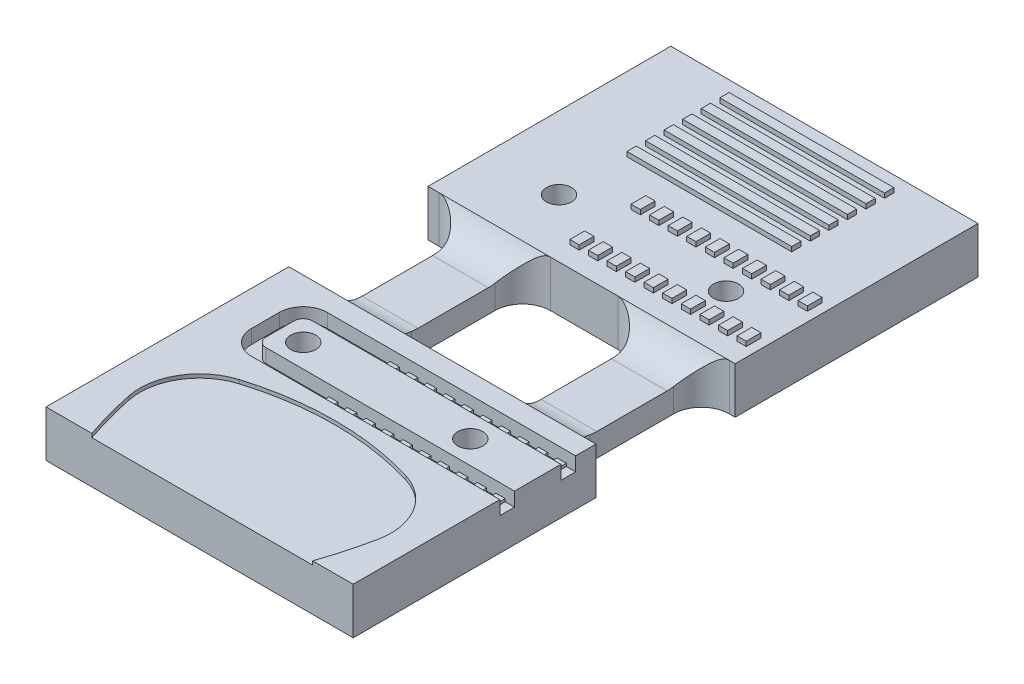
SolidWorks part; units mm, degrees
ref_plane "Front Plane" through (0, 0, 0) normal (0, 0, 1) x (1, 0, 0)
ref_plane "Top Plane" through (0, 0, 0) normal (0, 1, 0) x (1, 0, 0)
ref_plane "Right Plane" through (0, 0, 0) normal (1, 0, 0) x (0, 0, -1)
sketch "Pick" plane through (0, 0, 0) normal (0, 1, 0) x (1, 0, 0)
  line L0 (0, 0) -> (0, 30.62) construction
  line L1 (-13.11, 22.1848) -> (0, 22.1848) construction
  line L2 (0, 22.1848) -> (13.11, 22.1848) construction
  line L3 (0, 2.9) -> (-2.9, 2.9) construction
  line L6 (9.0762, 10.7993) -> (9.4821, 11.5846) construction
  line L7 (-7.0973, 23.4286) -> (-12.0562, 27.0493) construction
  arc A0 (-8.8774, 29.3049) -> (8.8774, 29.3049) centre (0, 0) cw
  arc A1 (-2.1219, 0.9232) -> (-13.11, 22.1848) centre (30.3499, 31.175) cw
  arc A2 (-13.11, 22.1848) -> (-8.8774, 29.3049) centre (-7.0973, 23.4286) cw
  arc A3 (2.1219, 0.9232) -> (13.11, 22.1848) centre (-30.3499, 31.175) ccw
  arc A4 (13.11, 22.1848) -> (8.8774, 29.3049) centre (7.0973, 23.4286) ccw
  arc A5 (-2.1219, 0.9232) -> (2.1219, 0.9232) centre (0, 2.9) ccw
  circle A6 centre (-7.0973, 23.4286) radius 6.14 construction
  circle A7 centre (-30.3499, 31.175) radius 44.38 construction
  circle A8 centre (0, 2.9) radius 2.9 construction
  point P8 (0, 30.62)
  dimension "D1" = 30.62
  dimension "D2" = 26.22
  dimension "D3" = 44.38
  dimension "D4" = 6.14
  dimension "D5" = 2.9
sketch "Sketch3" plane through (0, 0, 0) normal (0, 1, 0) x (1, 0, 0)
  line L0 (-11.8929, 16.62) -> (11.8929, 16.62)
  line L1 (-13.11, 22.1848) -> (-14, 26.4873) construction
  line L2 (0, 16.62) -> (0, 22.1848) construction
  line L3 (0, 22.1848) -> (13.11, 22.1848) construction
  line L4 (0, 0) -> (0, 30.62) construction
  line L5 (0, 30.92) -> (0, 30.62) construction
  line L6 (-11.8929, 16.62) -> (-10.1999, 11.7063) construction
  line L7 (-13.11, 22.1848) -> (-13.4038, 22.124) construction
  line L8 (-11.8929, 16.62) -> (-11.6093, 16.7177) construction
  line L9 (-8.8774, 29.3049) -> (-11.642, 28.4674) construction
  line L10 (-8.8774, 29.3049) -> (-8.9644, 29.592) construction
  line L11 (-11.8929, 16.62) -> (-16.8356, 16.62)
  line L12 (-16.8356, 16.62) -> (-16.8356, 42.7863)
  line L13 (-16.8356, 42.7863) -> (16.2633, 42.7863)
  line L14 (16.2633, 42.7863) -> (16.2633, 16.62)
  line L15 (16.2633, 16.62) -> (11.8929, 16.62)
  line L16 (0, 40.595) -> (0, 42.7863) construction
  line L17 (0, 30.62) -> (0, 22.1848) construction
  line L33 (16.2633, 32.42) -> (-10.5, 32.42)
  line L34 (-13.0875, 35.0075) -> (-13.0875, 38.0075)
  line L35 (-11.5, 35.0075) -> (-11.5, 38.0075)
  line L36 (-10.5, 34.0075) -> (16.2633, 34.0075)
  line L37 (16.2633, 34.0075) -> (16.2633, 32.42)
  line L38 (-10.5, 39.0075) -> (16.2633, 39.0075)
  line L39 (16.2633, 39.0075) -> (16.2633, 40.595)
  line L40 (16.2633, 40.595) -> (-10.5, 40.595)
  line L41 (-13.0875, 35.0075) -> (-11.5, 35.0075) construction
  line L42 (-11.5, 38.0075) -> (-13.0875, 38.0075) construction
  line L43 (0, 30.92) -> (0, 32.42) construction
  line L44 (0, 34.0075) -> (0, 36.5075) construction
  line L45 (-9, 36.5075) -> (9, 36.5075) construction
  line L46 (-9, 36.5075) -> (-11.5, 36.5075) construction
  line L47 (0, 36.5075) -> (0, 39.0075) construction
  arc A0 (-11.8929, 16.62) -> (-13.4038, 22.124) centre (30.3499, 31.175) cw
  arc A1 (2.1219, 0.9232) -> (13.11, 22.1848) centre (-30.3499, 31.175) ccw construction
  arc A2 (11.8929, 16.62) -> (13.4038, 22.124) centre (-30.3499, 31.175) ccw
  arc A3 (-8.9644, 29.592) -> (8.9644, 29.592) centre (0, 0) cw
  arc A4 (-13.11, 22.1848) -> (-2.1219, 0.9232) centre (30.3499, 31.175) ccw construction
  arc A5 (8.8774, 29.3049) -> (-8.8774, 29.3049) centre (0, 0) ccw construction
  arc A7 (-13.4038, 22.124) -> (-8.9644, 29.592) centre (-7.0973, 23.4286) cw
  arc A8 (8.9644, 29.592) -> (13.4038, 22.124) centre (7.0973, 23.4286) cw
  arc A12 (-10.5, 34.0075) -> (-11.5, 35.0075) centre (-10.5, 35.0075) cw
  arc A13 (-10.5, 32.42) -> (-13.0875, 35.0075) centre (-10.5, 35.0075) cw
  arc A14 (-11.5, 38.0075) -> (-10.5, 39.0075) centre (-10.5, 38.0075) cw
  arc A15 (-10.5, 40.595) -> (-13.0875, 38.0075) centre (-10.5, 38.0075) ccw
  point P26 (-9, 36.5075)
  point P38 (0, 42.7863)
  point P42 (9, 36.5075)
  point P95 (0, 36.5075)
  dimension "D2" = 0.3
  dimension "D3" = 18
  dimension "D7" = 1
  dimension "D1" = 14
  dimension "D8" = 1.5875
  dimension "D9" = 1.5
  dimension "D10" = 2.5
extrude "Boss-Extrude1" add sketch "Sketch3" against normal blind 0.4 contours A3 A8 A2 L15 L14 L13 L12 L11 A0 A7 | L40 A15 L34 A13 L33 L14 L36 A12 L35 A14 L38 | A14 L35 A12 L36 L14 L38 region at (-2.3245, 0, -31.7034) region at (2.8816, 0, -32.7247) region at (2.424, 0, -36.5075)
extrude "Boss-Extrude4" add sketch "Sketch3<5>" against normal blind 4.6 from surface contours A3 A8 A2 L15 L14 L13 L12 L11 A0 A7 | A8 A3 A7 A0 L0 A2 | L40 A15 L34 A13 L33 L14 L36 A12 L35 A14 L38 | A14 L35 A12 L36 L14 L38 region at (0, 0, -23.3328) region at (-2.3245, 0, -31.7034) region at (2.8816, 0, -32.7247) region at (2.424, 0, -36.5075) starting at face at (-0.1145, -0.4, -25.8487)
sketch "Sketch3<5>" plane through (0, 0, 0) normal (0, 1, 0) x (1, 0, 0) same geometry as "Sketch3"
extrude "Cut-Extrude2" cut sketch "Sketch3<7>" against normal blind 1.5 contours L40 A15 L34 A13 L33 L14 L36 A12 L35 A14 L38 region at (2.8816, 0, -32.7247)
sketch "Sketch3<7>" plane through (0, 0, 0) normal (0, 1, 0) x (1, 0, 0) same geometry as "Sketch3"
hole_wizard "M2.5 Clearance Hole1" positions "Sketch6" profile "Sketch7" hole size "M2.5" standard "ANSI Metric"
sketch "Sketch6" plane through (0, 0, 0) normal (0, 1, 0) x (1, 0, 0)
  point P0 (-9, 36.5075)
  point P3 (9, 36.5075)
sketch "Sketch7" plane through (-9, 0, -36.5075) normal (1, 0, 0) x (0, 0, 1)
  line L0 (0, 0) -> (0, 12)
  line L1 (0, 12) -> (1.35, 11.1888)
  line L2 (1.35, 11.1888) -> (1.35, 0)
  line L5 (1.35, 0) -> (0, 0)
  line L10 (0, 12) -> (-1.35, 11.1888) construction
  line L11 (0, -6.35) -> (0, 107.95) construction
  dimension "Hole Dia." = 2.7
  dimension "Hole Depth" = 12
  dimension "Drill Angle" = 118
sketch "Sketch8" plane through (0, 0, 0) normal (0, 1, 0) x (1, 0, 0)
  line L0 (0, 42.7863) -> (0, 57.7863) construction
  line L1 (-16.8356, 57.7863) -> (16.2633, 57.7863)
  line L2 (-16.8356, 57.7863) -> (-16.8356, 83.9526)
  line L3 (-16.8356, 83.9526) -> (16.2633, 83.9526)
  line L4 (16.2633, 57.7863) -> (16.2633, 83.9526)
  line L5 (0, 57.7863) -> (0, 59.9776) construction
  line L6 (0, 61.5651) -> (0, 64.0651) construction
  line L7 (0, 68.1526) -> (0, 69.6526) construction
  line L8 (0, 30.92) -> (0, 32.42) construction
  line L9 (0, 64.0651) -> (0, 66.5651) construction
  line L10 (0, 34.0075) -> (0, 36.5075) construction
  line L11 (0, 36.5075) -> (0, 39.0075) construction
  line L12 (0, 40.595) -> (0, 42.7863) construction
  line L13 (16.2633, 42.7863) -> (16.2633, 57.7863) construction
  line L14 (-16.8356, 42.7863) -> (-16.8356, 57.7863) construction
  line L15 (-16.8356, 16.62) -> (-16.8356, 42.7863) construction
  line L16 (16.2633, 59.9776) -> (-10.5, 59.9776) construction
  line L17 (-10.5, 59.9776) -> (-10.5, 61.5651) construction
  line L18 (-10.5, 61.5651) -> (16.2633, 61.5651) construction
  line L19 (16.2633, 66.5651) -> (-10.5, 66.5651) construction
  line L20 (-10.5, 66.5651) -> (-10.5, 68.1526) construction
  line L21 (-10.5, 68.1526) -> (16.2633, 68.1526) construction
  line L22 (-10.5, 40.595) -> (-10.5, 59.9776) construction
  line L23 (-10.5, 39.0075) -> (-10.5, 40.595) construction
  line L24 (-9, 64.0651) -> (9, 64.0651) construction
  line L25 (-9, 36.5075) -> (9, 36.5075) construction
  point P40 (0, 64.0651)
  point P44 (0, 59.4153)
  point P47 (-9, 64.0651)
  point P48 (9, 64.0651)
  dimension "D1" = 15
extrude "Boss-Extrude5" add sketch "Sketch8" against normal blind 5 separate body
hole_wizard "M2.5 Clearance Hole2" positions "Sketch9" profile "Sketch10" hole size "M2.5" standard "ANSI Metric"
sketch "Sketch9" plane through (0, 0, 0) normal (0, 1, 0) x (1, 0, 0)
  point P0 (-9, 64.0651)
  point P3 (9, 64.0651)
sketch "Sketch10" plane through (-9, 0, -64.0651) normal (1, 0, 0) x (0, 0, 1)
  line L0 (0, 0) -> (0, 12)
  line L1 (0, 12) -> (1.35, 11.1888)
  line L2 (1.35, 11.1888) -> (1.35, 0)
  line L5 (1.35, 0) -> (0, 0)
  line L10 (0, 12) -> (-1.35, 11.1888) construction
  line L11 (0, -6.35) -> (0, 107.95) construction
  dimension "Hole Dia." = 2.7
  dimension "Hole Depth" = 12
  dimension "Drill Angle" = 118
sketch "Sketch11" plane through (0, 0, 0) normal (0, 1, 0) x (1, 0, 0)
  line L0 (-10.5, 68.1526) -> (16.2633, 68.1526) construction
  line L1 (15.2633, 68.1526) -> (14.2633, 68.1526)
  line L2 (15.2633, 68.1526) -> (15.2633, 66.5651)
  line L3 (15.2633, 66.5651) -> (14.2633, 66.5651)
  line L4 (14.2633, 68.1526) -> (14.2633, 66.5651)
  line L5 (16.2633, 66.5651) -> (-10.5, 66.5651) construction
  line L6 (-10.5, 61.5651) -> (16.2633, 61.5651) construction
  line L7 (15.2633, 61.5651) -> (14.2633, 61.5651)
  line L8 (15.2633, 61.5651) -> (15.2633, 59.9776)
  line L9 (15.2633, 59.9776) -> (14.2633, 59.9776)
  line L10 (14.2633, 61.5651) -> (14.2633, 59.9776)
  line L11 (16.2633, 59.9776) -> (-10.5, 59.9776) construction
  line L12 (16.2633, 40.595) -> (-10.5, 40.595) construction
  line L13 (15.2633, 40.595) -> (14.2633, 40.595)
  line L14 (15.2633, 40.595) -> (15.2633, 39.0075)
  line L15 (15.2633, 39.0075) -> (14.2633, 39.0075)
  line L16 (14.2633, 40.595) -> (14.2633, 39.0075)
  line L17 (-10.5, 39.0075) -> (16.2633, 39.0075) construction
  line L18 (-10.5, 34.0075) -> (16.2633, 34.0075) construction
  line L19 (15.2633, 34.0075) -> (14.2633, 34.0075)
  line L20 (15.2633, 34.0075) -> (15.2633, 32.42)
  line L21 (15.2633, 32.42) -> (14.2633, 32.42)
  line L22 (14.2633, 34.0075) -> (14.2633, 32.42)
  line L23 (16.2633, 32.42) -> (-10.5, 32.42) construction
  line L24 (16.2633, 66.5651) -> (15.2633, 66.5651) construction
  line L25 (14.2633, 66.5651) -> (14.2633, 61.5651) construction
  line L26 (14.2633, 59.9776) -> (14.2633, 40.595) construction
  line L27 (14.2633, 39.0075) -> (14.2633, 34.0075) construction
  line L28 (0, 69.6526) -> (0, 71.2677) construction
  line L29 (-8.8774, 71.2677) -> (8.8774, 71.2677)
  line L30 (-8.8774, 71.2677) -> (-8.8774, 72.2677)
  line L31 (-8.8774, 72.2677) -> (8.8774, 72.2677)
  line L32 (8.8774, 71.2677) -> (8.8774, 72.2677)
  line L33 (-8.8774, 29.3049) -> (8.8774, 29.3049) construction
  line L34 (0, 30.62) -> (0, 22.1848) construction
  line L35 (0, 29.3049) -> (0, 30.92) construction
  point P47 (0, 29.3049)
  dimension "D1" = 1
extrude "Boss-Extrude6" add sketch "Sketch11" along normal blind 0.5 contours L2 L3 L4 L1 | L8 L9 L10 L7
pattern_linear "LPattern1" count 10 spacing 2 along (-1, 0, 0) of "Boss-Extrude6"
extrude "Boss-Extrude7" add sketch "Sketch11<3>" along normal blind 0.3 from surface contours L13 L16 L15 L14 | L19 L22 L21 L20 region at (14.7633, 0, -39.8013) region at (14.7633, 0, -33.2138) starting at face at (-2.3007, -1.5, -36.5075)
sketch "Sketch11<3>" plane through (0, 0, 0) normal (0, 1, 0) x (1, 0, 0) same geometry as "Sketch11"
pattern_linear "LPattern2" count 10 spacing 2 along (-1, 0, 0) of "Boss-Extrude7"
extrude "Boss-Extrude8" add sketch "Sketch11<4>" along normal blind 0.5 contours L29 L32 L31 L30
sketch "Sketch11<4>" plane through (0, 0, 0) normal (0, 1, 0) x (1, 0, 0) same geometry as "Sketch11"
pattern_linear "LPattern3" count 6 spacing 2 along (0, 0, -1) of "Boss-Extrude8"
sketch "Sketch12" plane through (0, -5, 0) normal (0, -1, 0) x (1, 0, 0)
  line L0 (-16.8356, -57.7863) -> (16.2633, -57.7863) construction
  line L1 (-12.6336, -57.7863) -> (-6.6336, -57.7863)
  line L2 (-12.6336, -57.7863) -> (-12.6336, -42.7863)
  line L3 (-12.6336, -42.7863) -> (-6.6336, -42.7863)
  line L4 (-6.6336, -57.7863) -> (-6.6336, -42.7863)
  line L5 (-16.8356, -42.7863) -> (16.2633, -42.7863) construction
  line L6 (-6.6336, -42.7863) -> (6.6336, -42.7863) construction
  line L7 (6.6336, -57.7863) -> (12.6336, -57.7863)
  line L8 (6.6336, -57.7863) -> (6.6336, -42.7863)
  line L9 (6.6336, -42.7863) -> (12.6336, -42.7863)
  line L10 (12.6336, -57.7863) -> (12.6336, -42.7863)
  point P12 (0, -42.7863)
  dimension "D1" = 6
extrude "Boss-Extrude9" add sketch "Sketch12" against normal blind 2.5
fillet "Fillet1" radius 3 8 edges at (12.6336, -3.75, -42.7863) (-6.6336, -3.75, -42.7863) (6.6336, -3.75, -42.7863) (-12.6336, -3.75, -42.7863) (-12.6336, -3.75, -57.7863) (6.6336, -3.75, -57.7863) (-6.6336, -3.75, -57.7863) (12.6336, -3.75, -57.7863)
fillet "Fillet2" radius 4 4 edges at (9.6336, -2.5, -57.7863) (-9.6336, -2.5, -57.7863) (-9.6336, -2.5, -42.7863) (9.6336, -2.5, -42.7863)
